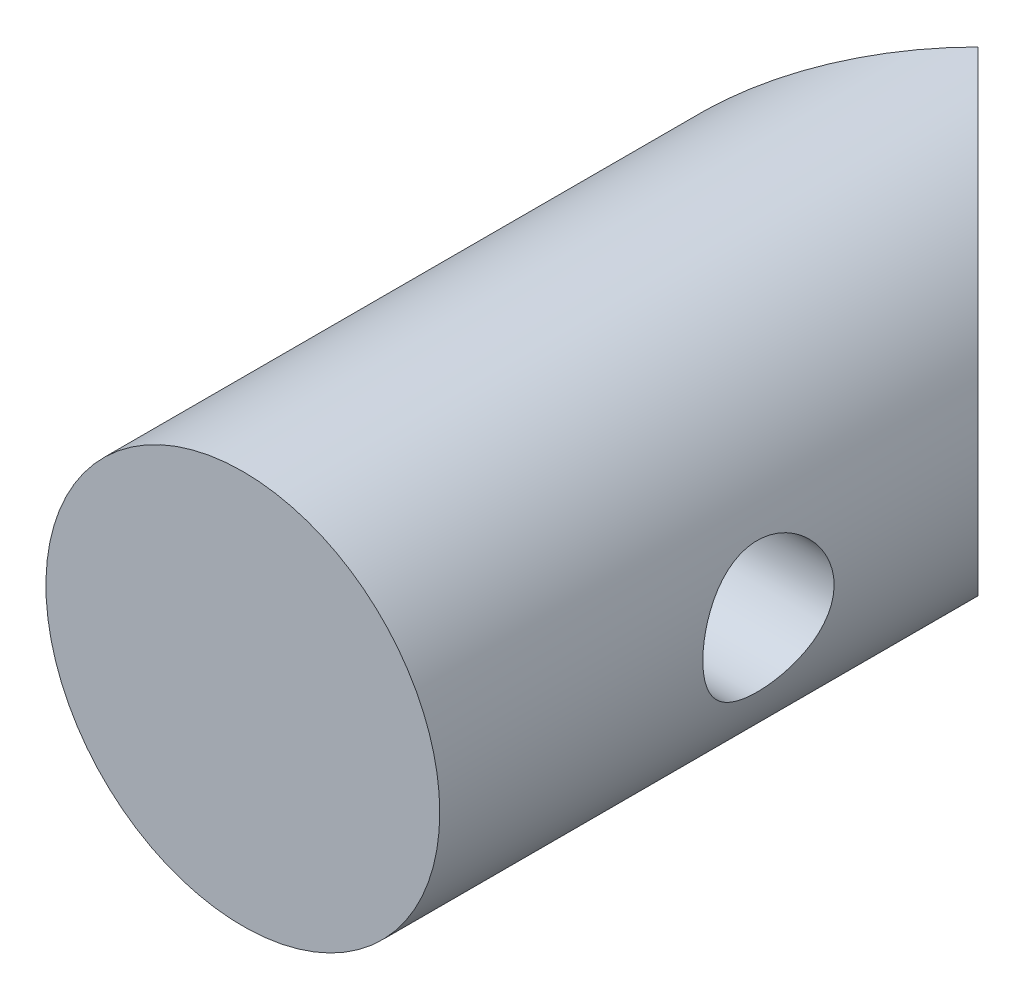
SolidWorks part; units mm, degrees
material "Alloy Steel"
ref_plane "Front Plane" through (0, 0, 0) normal (0, 0, 1) x (1, 0, 0)
ref_plane "Top Plane" through (0, 0, 0) normal (0, 1, 0) x (1, 0, 0)
ref_plane "Right Plane" through (0, 0, 0) normal (1, 0, 0) x (0, 0, -1)
sketch "Sketch1" plane through (0, 0, 0) normal (0, 0, 1) x (1, 0, 0)
  circle A0 centre (0, 0) radius 4.7625
  dimension "D1" = 9.525
extrude "Extrude1" add sketch "Sketch1" along normal blind 17.78
sketch "Sketch2" plane through (0, 0, 0) normal (0, 1, 0) x (1, 0, 0)
  line L0 (0, 0) -> (4.7625, -4.7625)
  line L1 (4.7625, -17.78) -> (4.7625, 0) construction
  line L2 (4.7625, -4.7625) -> (4.7625, 1.9052)
  line L3 (4.7625, 1.9052) -> (-4.7625, 1.9052)
  line L4 (-4.7625, 1.9052) -> (-4.7625, -4.7625)
  line L5 (-4.7625, 0) -> (-4.7625, -17.78) construction
  line L6 (-4.7625, -4.7625) -> (0, 0)
  dimension "D1" = 90
extrude "Extrude2" cut sketch "Sketch2" against normal through all and the other way through all
sketch "Sketch8" plane through (0, 0, 17.78) normal (0, 0, 1) x (1, 0, 0)
  line L0 (0, 0) -> (-4.7625, 0) construction
  circle A0 centre (0, 0) radius 4.7625 construction
ref_plane "Plane2" through (-4.7625, 0, 17.78) normal (-1, 0, 0) x (0, 0, 1)
sketch "Sketch3" plane through (-4.7625, 0, 0) normal (1, 0, 0) x (0, 0, -1)
  line L0 (0, 0) -> (-9.8298, 0) construction
  dimension "D1" = 9.8298
sketch "Sketch9" plane through (-4.7625, 0, 17.78) normal (-1, 0, 0) x (0, 0, 1)
  line L0 (0, 0) -> (-9.8298, 0) construction
  dimension "D1" = 9.8298
hole_wizard "1/8 (0.125) Diameter Hole4" positions "Sketch11" profile "Sketch12" hole size "1/8" standard "Ansi Inch" end condition through all
sketch "Sketch11" plane through (-4.7625, 0, 17.78) normal (-1, 0, 0) x (0, 0, 1)
  point P1 (-7.9502, 0)
sketch "Sketch12" plane through (-4.7625, 0, 9.8298) normal (0, 1, 0) x (0, 0, 1)
  line L0 (0, 0) -> (0, 9.525)
  line L1 (0, 9.525) -> (1.5875, 9.525)
  line L2 (1.5875, 9.525) -> (1.5875, 0)
  line L5 (1.5875, 0) -> (0, 0)
  line L11 (0, -6.35) -> (0, 107.95) construction
  dimension "Thru Hole Dia." = 3.175
  dimension "Thru Hole Depth" = 9.525
